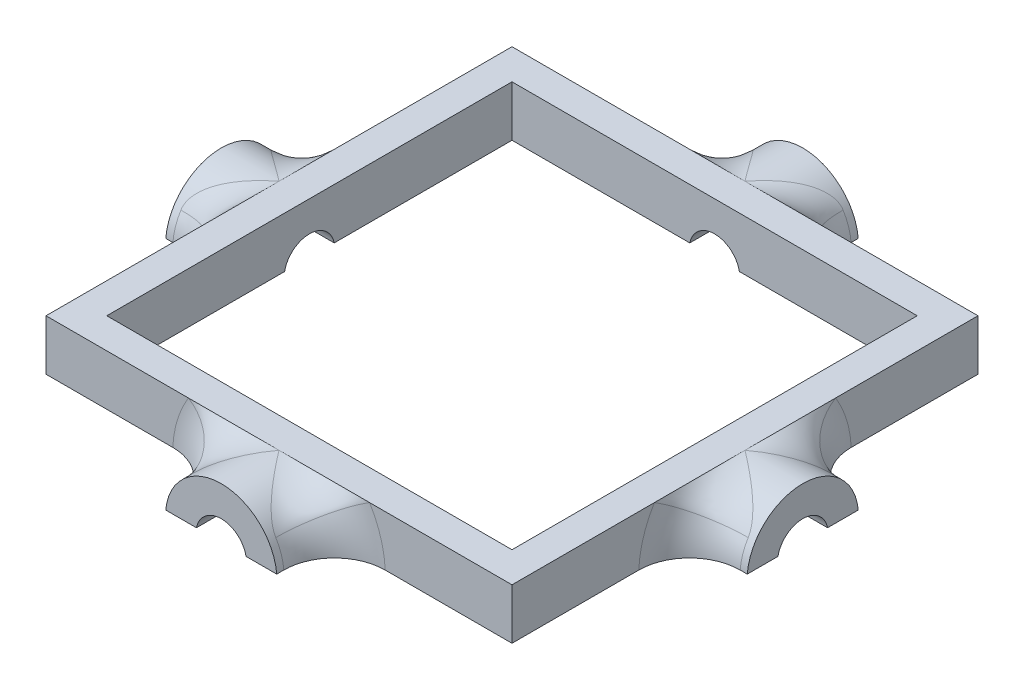
SolidWorks part; units mm, degrees
ref_plane "Front Plane" through (0, 0, 0) normal (0, 0, 1) x (1, 0, 0)
ref_plane "Top Plane" through (0, 0, 0) normal (0, 1, 0) x (1, 0, 0)
ref_plane "Right Plane" through (0, 0, 0) normal (1, 0, 0) x (0, 0, -1)
sketch "Sketch1" plane through (0, 0, 0) normal (0, 1, 0) x (1, 0, 0)
  line L1 (-20, 20) -> (20, 20)
  line L2 (-20, 20) -> (-20, -20)
  line L3 (-20, -20) -> (20, -20)
  line L4 (20, 20) -> (20, -20)
  line L5 (-23, 23) -> (23, 23)
  line L6 (-23, 23) -> (-23, -23)
  line L7 (-23, -23) -> (23, -23)
  line L8 (23, 23) -> (23, -23)
  point P8 (0, 20)
  point P10 (0, 23)
  point P11 (-20, 0)
  point P12 (-23, 0)
  dimension "D1" = 40
  dimension "D2" = 40
  dimension "D3" = 46
  dimension "D4" = 46
extrude "Boss-Extrude1" add sketch "Sketch1" along normal blind 5
sketch "Sketch2" plane through (-23, 0, 0) normal (-1, 0, 0) x (0, 0, 1)
  line L0 (-23, 0) -> (23, 0) construction
  line L1 (-5.4772, 0) -> (-2.4495, 0)
  line L2 (5.4772, 0) -> (2.4495, 0)
  line L3 (0, 5) -> (0, 0) construction
  line L4 (-23, 5) -> (23, 5) construction
  arc A1 (-2.4495, 0) -> (2.4495, 0) centre (0, -0.5) cw
  arc A2 (-5.4772, 0) -> (5.4772, 0) centre (0, -0.5) cw
  dimension "D1" = 2.5
  dimension "D3" = 3
  dimension "D2" = 0.5
extrude "Boss-Extrude2" add sketch "Sketch2" along normal blind 5.7 contours L2 A1 L1 A2
ref_axis "Axis1" through (0, -0.25, 0) along (0, 1, 0)
sketch "Sketch3" plane through (-28.7, 0, 0) normal (-1, 0, 0) x (0, 0, 1)
  line L0 (0, -0.25) -> (0, 5.25) construction
  line L1 (-2.4495, 0) -> (2.4495, 0)
  arc A0 (-2.4495, 0) -> (2.4495, 0) centre (0, -0.5) cw
  arc A1 (2.4495, 0) -> (-2.4495, 0) centre (0, -0.5) ccw construction
  dimension "D1" = 0.5
extrude "Cut-Extrude1" cut sketch "Sketch3" against normal up to next
pattern_circular "CirPattern3" count 4 every 90 about axis through (0, -0.25, 0) along (0, 1, 0) of "Boss-Extrude2", "Cut-Extrude1"
fillet "Fillet4" radius 5 8 edges at (-23, 3.562, 3.7081) (3.7081, 3.562, -23) (-3.7081, 3.562, -23) (23, 3.562, 3.7081) (23, 3.562, -3.7081) (-3.7081, 3.562, 23) (3.7081, 3.562, 23) (-23, 3.562, -3.7081)
